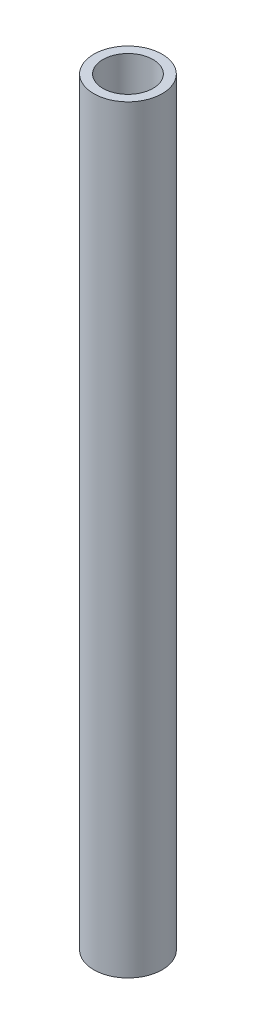
SolidWorks part; units mm, degrees
material "AISI 316 Stainless Steel Sheet (SS)"
ref_plane "Front Plane" through (0, 0, 0) normal (0, 0, 1) x (1, 0, 0)
ref_plane "Top Plane" through (0, 0, 0) normal (0, 1, 0) x (1, 0, 0)
ref_plane "Right Plane" through (0, 0, 0) normal (1, 0, 0) x (0, 0, -1)
sketch "Sketch1" plane through (0, 0, 0) normal (0, 1, 0) x (1, 0, 0)
  circle A0 centre (0, 0) radius 0.4508
  circle A1 centre (0, 0) radius 0.3302
  dimension "D1" = 0.6604
  dimension "D2" = 0.9017
extrude "Boss-Extrude1" add sketch "Sketch1" along normal blind 10 contours A0 A1 region at (-0.4381, 0, 0)
